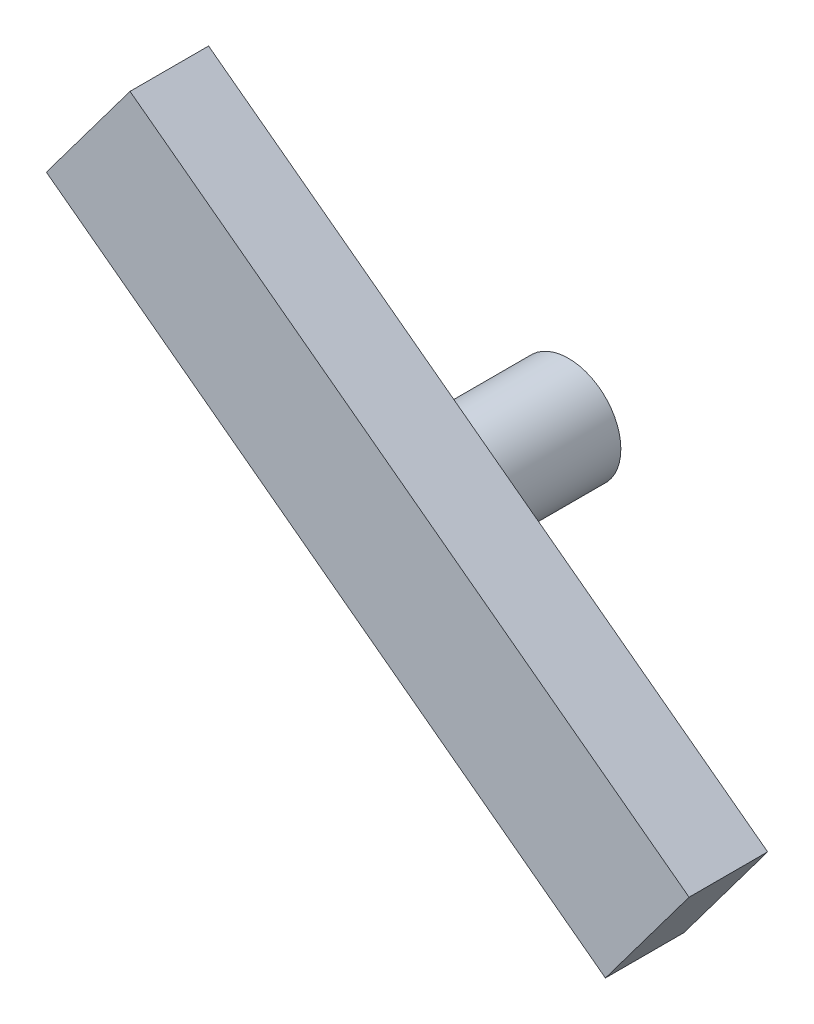
SolidWorks part; units mm, degrees
ref_plane "Alzado" through (0, 0, 0) normal (0, 0, 1) x (1, 0, 0)
ref_plane "Planta" through (0, 0, 0) normal (0, 1, 0) x (1, 0, 0)
ref_plane "Vista lateral" through (0, 0, 0) normal (1, 0, 0) x (0, 0, -1)
sketch3d "Sk_Vastago"
  line L0 (-263.1284, 316.5049, -22) -> (-263.1284, 316.5049, -15)
sweep "Vastago" add path "Sk_Vastago" circular profile diameter 6 parameters "D3"=6
sketch "Sk_Goma" plane through (0, 0, 0) normal (0, 0, 1) x (1, 0, 0)
  line L0 (-249.5118, 301.3198) -> (-244.7188, 307.725)
  line L1 (-244.7188, 307.725) -> (-276.7449, 331.6901)
  line L2 (-276.7449, 331.6901) -> (-281.538, 325.2848)
  line L3 (-281.538, 325.2848) -> (-249.5118, 301.3198)
extrude "Goma" add sketch "Sk_Goma" along normal blind 4.5 from offset 15 offset against normal yes
